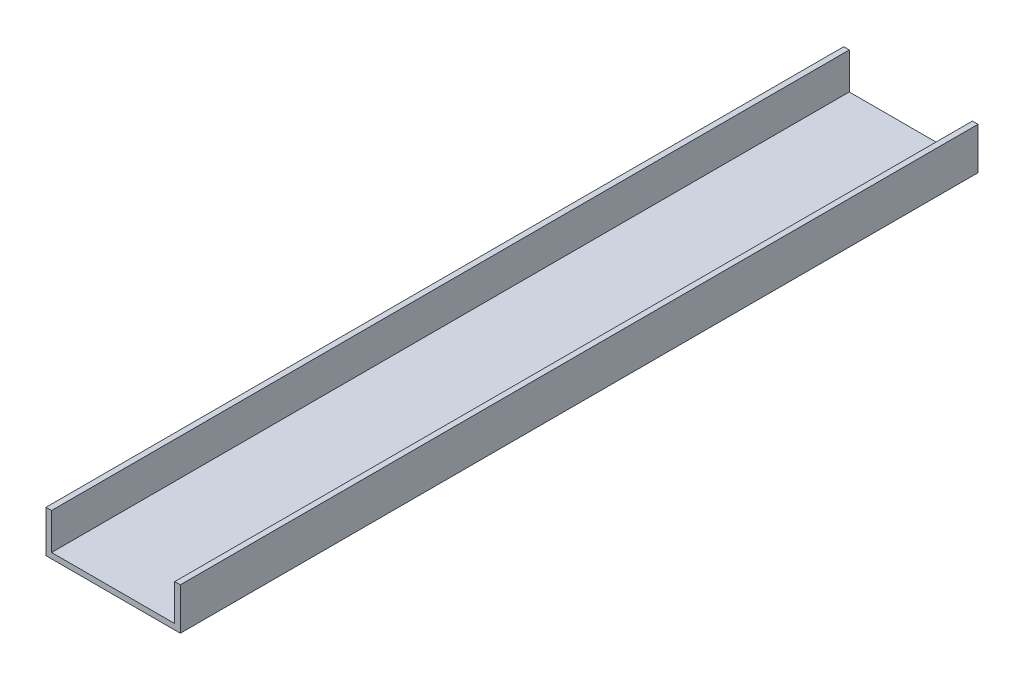
SolidWorks part; units mm, degrees
material "Corrugated Paper"
ref_plane "Front Plane" through (0, 0, 0) normal (0, 0, 1) x (1, 0, 0)
ref_plane "Top Plane" through (0, 0, 0) normal (0, 1, 0) x (1, 0, 0)
ref_plane "Right Plane" through (0, 0, 0) normal (1, 0, 0) x (0, 0, -1)
sketch "Sketch1" plane through (0, 0, 0) normal (0, 0, 1) x (1, 0, 0)
  line L0 (0, 0) -> (48, 0)
  line L1 (48, 0) -> (48, 15)
  line L2 (0, 0) -> (0, 15)
  dimension "D1" = 48
  dimension "D2" = 15
  dimension "D3" = 15
extrude "Extrude-Thin1" add sketch "Sketch1" along normal blind 285 thin thin type one direction wall 2
